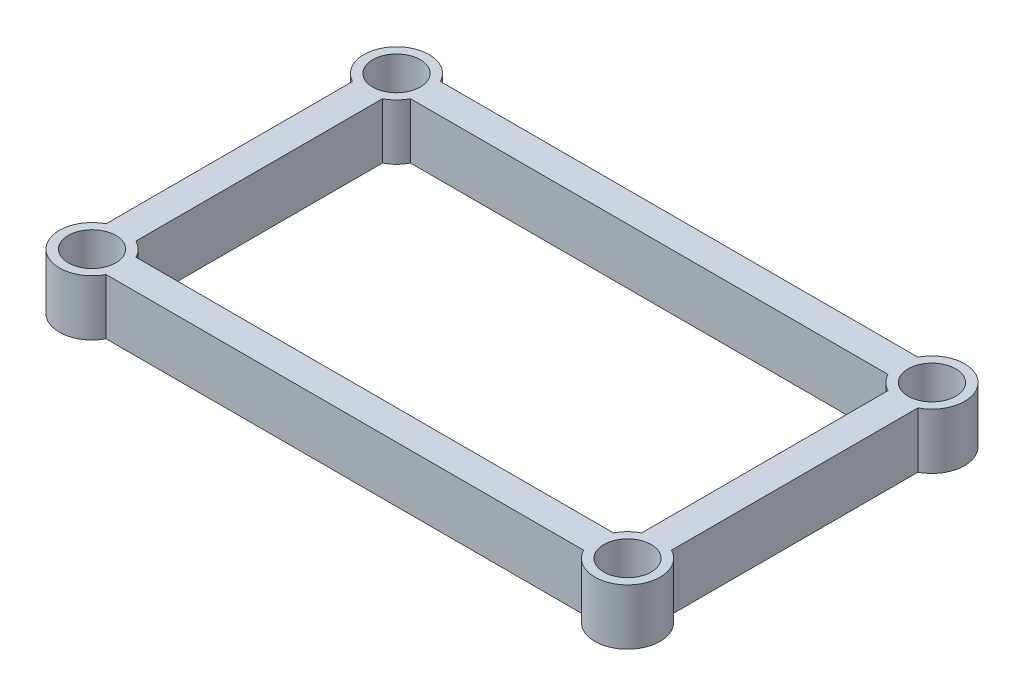
SolidWorks part; units mm, degrees
material "Gray Cast Iron"
ref_plane "Front Plane" through (0, 0, 0) normal (0, 0, 1) x (1, 0, 0)
ref_plane "Top Plane" through (0, 0, 0) normal (0, 1, 0) x (1, 0, 0)
ref_plane "Right Plane" through (0, 0, 0) normal (1, 0, 0) x (0, 0, -1)
sketch "Sketch1" plane through (0, 0, 0) normal (0, 1, 0) x (1, 0, 0)
  line L0 (-208, -123) -> (208, -123)
  line L1 (208, -123) -> (208, 123)
  line L2 (208, 123) -> (-208, 123)
  line L3 (-208, 123) -> (-208, -123)
extrude "Boss-Extrude1" add sketch "Sketch1" along normal mid plane 41
sketch "Sketch2" plane through (0, 0, 0) normal (0, 1, 0) x (1, 0, 0)
  line L0 (-186, -101) -> (186, -101)
  line L1 (186, -101) -> (186, 101)
  line L2 (186, 101) -> (-186, 101)
  line L3 (-186, 101) -> (-186, -101)
extrude "Cut-Extrude1" cut sketch "Sketch2" against normal mid plane 60
sketch "Sketch3" plane through (0, 0, 0) normal (0, 1, 0) x (1, 0, 0)
  circle A0 centre (-197, -112) radius 24
  circle A1 centre (-197, 112) radius 24
  circle A2 centre (197, -112) radius 24
  circle A3 centre (197, 112) radius 24
  dimension "D1" = 48
  dimension "D2" = 48
  dimension "D3" = 48
  dimension "D4" = 48
extrude "Boss-Extrude2" add sketch "Sketch3" along normal mid plane 41
sketch "Sketch4" plane through (0, 0, 0) normal (0, 1, 0) x (1, 0, 0)
  circle A0 centre (-197, -112) radius 17.5
  circle A1 centre (-197, 112) radius 17.5
  circle A2 centre (197, -112) radius 17.5
  circle A3 centre (197, 112) radius 17.5
  dimension "D1" = 35
  dimension "D2" = 35
  dimension "D3" = 35
  dimension "D4" = 35
extrude "Cut-Extrude2" cut sketch "Sketch4" against normal mid plane 60
